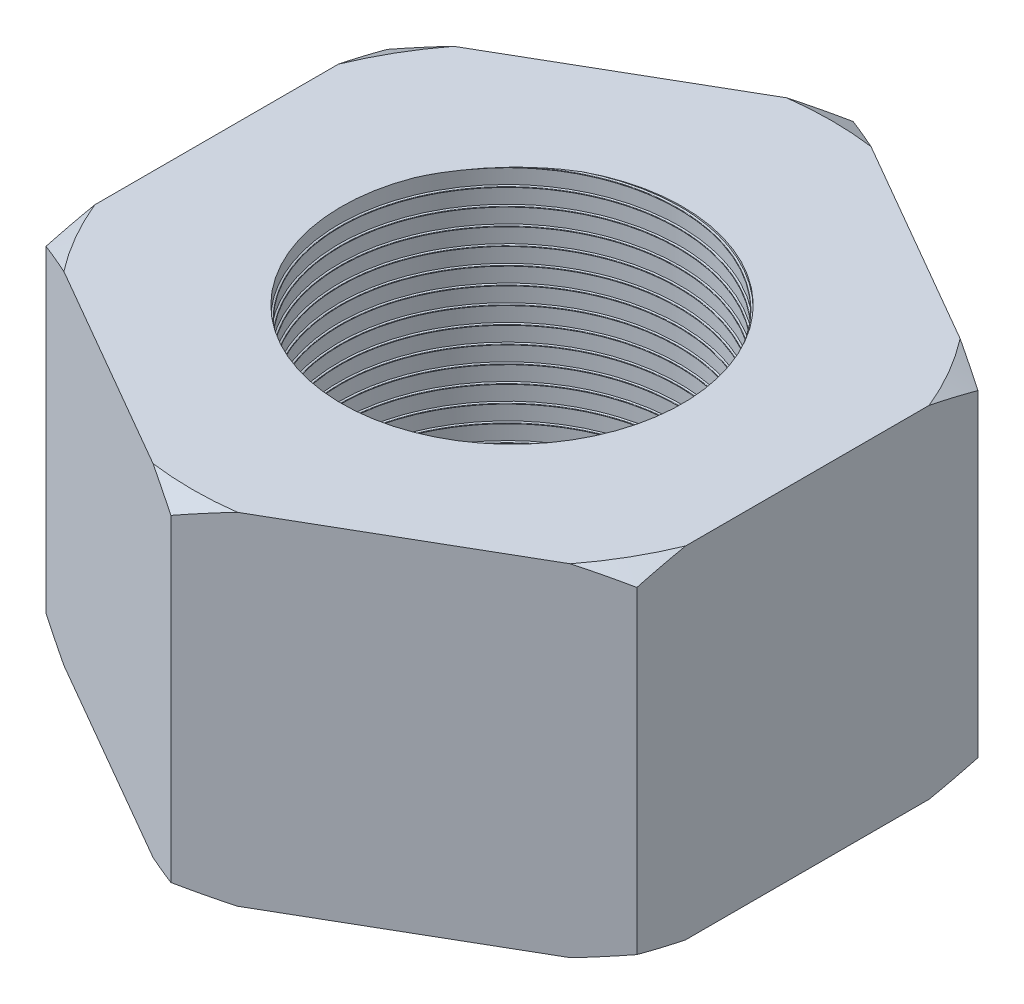
SolidWorks part; units mm, degrees
ref_plane "Front Plane" through (0, 0, 0) normal (0, 0, 1) x (1, 0, 0)
ref_plane "Top Plane" through (0, 0, 0) normal (0, 1, 0) x (1, 0, 0)
ref_plane "Right Plane" through (0, 0, 0) normal (1, 0, 0) x (0, 0, -1)
sketch "Sketch1" plane through (0, 0, 0) normal (0, 1, 0) x (1, 0, 0)
  line L1 (0, -20) -> (17.3205, -10)
  line L2 (17.3205, -10) -> (17.3205, 10)
  line L3 (17.3205, 10) -> (0, 20)
  line L4 (0, 20) -> (-17.3205, 10)
  line L5 (-17.3205, 10) -> (-17.3205, -10)
  line L6 (-17.3205, -10) -> (0, -20)
  circle A0 centre (0, 0) radius 17.3205 construction
  dimension "D1" = 20
extrude "Boss-Extrude1" add sketch "Sketch1" along normal blind 20
sketch "Sketch3" plane through (0, 20, 0) normal (0, 1, 0) x (1, 0, 0)
  circle A0 centre (0, 0) radius 10
  dimension "D1" = 20
extrude "Cut-Extrude1" cut sketch "Sketch3" against normal blind 20
sketch "Sketch5" plane through (0, 0, 0) normal (1, 0, 0) x (0, 0, -1)
  line L0 (18.3865, 20.7654) -> (22.1388, 20.7654)
  line L1 (22.1388, 20.7654) -> (22.1388, 18.1715)
  line L2 (22.1388, 18.1715) -> (17.3098, 20.7654)
  line L3 (17.3098, 20.7654) -> (18.3865, 20.7654)
  line L4 (0, 23.295) -> (0, -5.929) construction
  line L5 (-28.5777, 10) -> (23.4834, 10) construction
  line L6 (-10, 20) -> (10, 20) construction
  line L7 (17.3098, -0.7654) -> (18.3865, -0.7654)
  line L8 (22.1388, 1.8285) -> (17.3098, -0.7654)
  line L9 (22.1388, -0.7654) -> (22.1388, 1.8285)
  line L10 (18.3865, -0.7654) -> (22.1388, -0.7654)
  dimension "D1" = 10
revolve "Cut-Revolve1" cut sketch "Sketch5" angle 360 about L4
sketch "Sketch8" plane through (0, 20, 0) normal (0, 1, 0) x (1, 0, 0)
  circle A0 centre (0, 0) radius 10 construction
  circle A1 centre (0, 0) radius 10
curve "Helix/Spiral1" pitch 1 height 20 turns 20
sketch "Sketch9" plane through (0, 0, 0) normal (0, 0, 1) x (1, 0, 0)
  line L0 (-10.0315, 0.1831) -> (-10.0315, 0.047)
  line L1 (-10.0315, 0.047) -> (-9.9103, 0.0923)
  line L2 (-9.9099, 0.1385) -> (-10.0315, 0.1831)
  arc A0 (-9.9099, 0.1385) -> (-9.9103, 0.0923) centre (-9.919, 0.1154) cw
  point P2 (-7.0089, -0.0241)
  point P3 (0, 0)
  point P5 (-7.0092, 0.0223)
  point P8 (0, 0)
sweep "Sweep1" add profiles "Sketch9" path "Helix/Spiral1"
